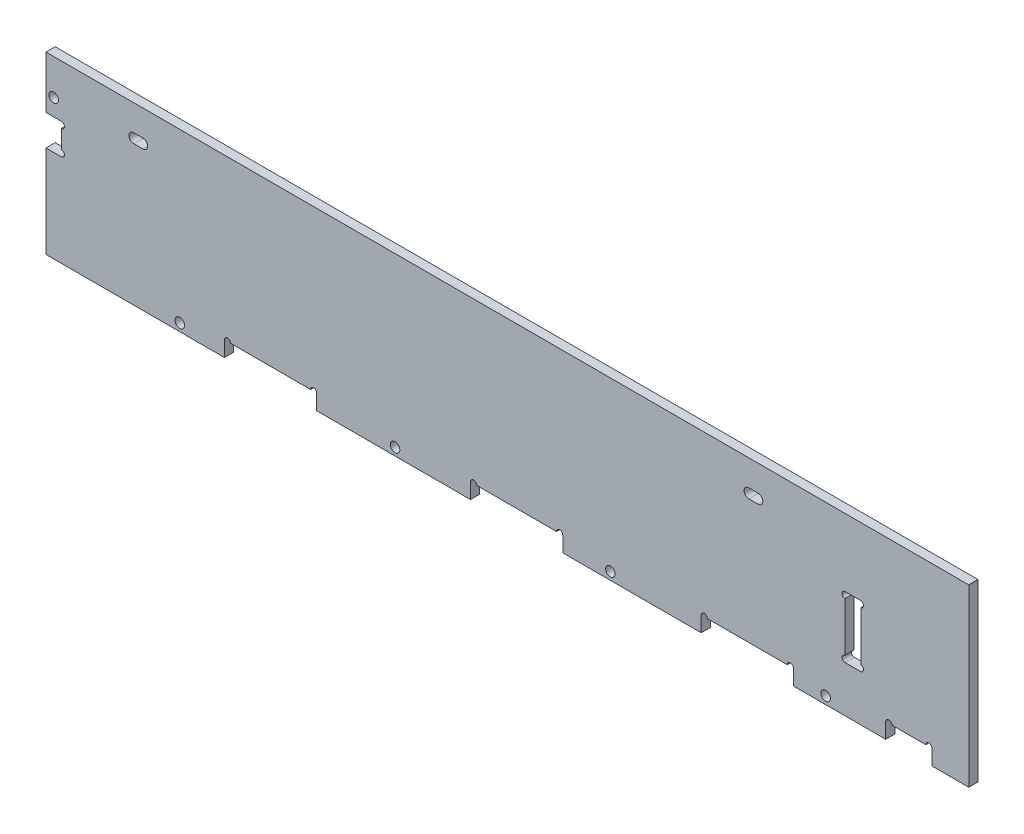
SolidWorks part; units mm, degrees
material "사용자정의 플라스틱"
ref_plane "정면" through (0, 0, 0) normal (0, 0, 1) x (1, 0, 0)
ref_plane "윗면" through (0, 0, 0) normal (0, 1, 0) x (1, 0, 0)
ref_plane "우측면" through (0, 0, 0) normal (1, 0, 0) x (0, 0, -1)
sketch "스케치1" plane through (0, 0, 0) normal (0, 0, 1) x (1, 0, 0)
  line L1 (0, 0) -> (300, 0)
  line L2 (0, 0) -> (0, 57)
  line L3 (0, 57) -> (300, 57)
  line L4 (300, 0) -> (300, 57)
  dimension "D1" = 57
  dimension "D2" = 300
extrude "보스-돌출1" add sketch "스케치1" along normal blind 3
sketch "스케치2" plane through (0, 0, 3) normal (0, 0, 1) x (1, 0, 0)
  line L0 (0, 57) -> (0, 0) construction
  line L1 (5, 40) -> (0, 40)
  line L2 (5, 40) -> (5, 30)
  line L3 (5, 30) -> (0, 30)
  line L4 (0, 40) -> (0, 30)
  line L5 (5, 30) -> (0, 30) construction
  line L6 (0, 0) -> (300, 0) construction
  line L7 (58, 5) -> (88, 5)
  line L8 (58, 5) -> (58, 0)
  line L9 (58, 0) -> (88, 0)
  line L10 (88, 5) -> (88, 0)
  line L11 (88, 5) -> (88, 0) construction
  line L12 (168, 5) -> (168, 0) construction
  line L13 (168, 0) -> (138, 0)
  line L14 (168, 0) -> (168, 5)
  line L15 (168, 5) -> (138, 5)
  line L16 (138, 0) -> (138, 5)
  line L17 (243, 5) -> (243, 0) construction
  line L18 (243, 0) -> (213, 0)
  line L19 (243, 0) -> (243, 5)
  line L20 (243, 5) -> (213, 5)
  line L21 (213, 0) -> (213, 5)
  line L22 (288, 5) -> (288, 0) construction
  line L23 (288, 0) -> (273, 0)
  line L24 (288, 0) -> (288, 5)
  line L25 (288, 5) -> (273, 5)
  line L26 (273, 0) -> (273, 5)
  line L28 (259.8, 35) -> (264.8, 35)
  line L29 (259.8, 35) -> (259.8, 15)
  line L30 (259.8, 15) -> (264.8, 15)
  line L31 (264.8, 35) -> (264.8, 15)
extrude "컷-돌출1" cut sketch "스케치2" against normal blind 5
sketch "스케치3" plane through (0, 0, 3) normal (0, 0, 1) x (1, 0, 0)
  line L0 (264.8, 35) -> (259.8, 35) construction
  line L1 (259.8, 15) -> (264.8, 15) construction
  line L2 (264.8, 15) -> (264.8, 35) construction
  line L3 (259.8, 35) -> (259.8, 15) construction
  line L4 (243, 5) -> (213, 5) construction
  line L5 (88, 5) -> (58, 5) construction
  line L6 (168, 5) -> (138, 5) construction
  line L7 (5, 30) -> (5, 40) construction
  line L8 (288, 5) -> (273, 5) construction
  line L9 (273, 5) -> (273, 0) construction
  line L10 (288, 0) -> (288, 5) construction
  circle A0 centre (274, 5) radius 1
  circle A1 centre (287, 5) radius 1
  circle A2 centre (259.8, 16) radius 1
  circle A3 centre (264.8, 16) radius 1
  circle A4 centre (264.8, 34) radius 1
  circle A5 centre (259.8, 34) radius 1
  circle A6 centre (214, 5) radius 1
  circle A7 centre (242, 5) radius 1
  circle A8 centre (87, 5) radius 1
  circle A9 centre (139, 5) radius 1
  circle A10 centre (167, 5) radius 1
  circle A11 centre (5, 31) radius 1
  circle A12 centre (5, 39) radius 1
  circle A13 centre (59, 5) radius 1
  dimension "D1" = 2
  dimension "D2" = 2
extrude "컷-돌출2" cut sketch "스케치3" against normal blind 5
sketch "스케치4" plane through (0, 0, 0) normal (0, 0, -1) x (-1, 0, 0)
  line L0 (-45.0287, 2.5) -> (-41.9287, 2.5) construction
  line L1 (-2.5, 43.9) -> (-2.5, 47) construction
  line L2 (-5, 43.9) -> (0, 43.9) construction
  line L3 (-45.0287, 5) -> (-45.0287, 0) construction
  line L4 (-5, 47) -> (0, 47) construction
  line L6 (-41.9287, 5) -> (-41.9287, 0) construction
  line L9 (-115.0287, 2.5) -> (-111.9287, 2.5) construction
  line L10 (-115.0287, 5) -> (-115.0287, 0) construction
  line L11 (-111.9287, 5) -> (-111.9287, 0) construction
  line L12 (-185.0287, 2.5) -> (-181.9287, 2.5) construction
  line L13 (-185.0287, 5) -> (-185.0287, 0) construction
  line L14 (-181.9287, 5) -> (-181.9287, 0) construction
  line L15 (-255.0287, 2.5) -> (-251.9287, 2.5) construction
  line L16 (-255.0287, 5) -> (-255.0287, 0) construction
  line L17 (-251.9287, 5) -> (-251.9287, 0) construction
  circle A0 centre (-253.4787, 2.5) radius 1.55
  circle A1 centre (-183.4787, 2.5) radius 1.55
  circle A2 centre (-113.4787, 2.5) radius 1.55
  circle A3 centre (-43.4787, 2.5) radius 1.55
  circle A4 centre (-2.5, 45.45) radius 1.55
extrude "컷-돌출3" cut sketch "스케치4" against normal blind 10
sketch "스케치5" plane through (0, 0, 3) normal (0, 0, 1) x (1, 0, 0)
  line L0 (43.45, 57) -> (43.45, 49)
  line L1 (46.55, 45) -> (43.45, 45) construction
  line L2 (47.75, 49) -> (47.75, 46.2) construction
  line L3 (43.45, 49) -> (43.45, 46.2) construction
  line L4 (46.55, 57) -> (43.45, 57)
  line L5 (47.75, 46.2) -> (46.55, 46.2)
  line L6 (46.55, 57) -> (46.55, 49)
  line L7 (42.25, 46.2) -> (42.25, 49) construction
  line L8 (46.55, 49) -> (47.75, 49)
  line L9 (46.55, 46.2) -> (46.55, 49) construction
  line L10 (43.45, 46.2) -> (43.45, 45)
  line L11 (46.55, 49) -> (43.45, 49) construction
  line L12 (46.55, 46.2) -> (43.45, 46.2) construction
  line L13 (43.45, 46.2) -> (42.25, 46.2)
  line L14 (46.55, 46.2) -> (46.55, 45)
  line L15 (45, 45) -> (45, 43.45) construction
  line L16 (42.25, 49) -> (43.45, 49)
  line L17 (47.75, 47.6) -> (46.55, 47.6) construction
  line L18 (42.25, 47.6) -> (43.45, 47.6) construction
  line L19 (45, 46.2) -> (45, 45) construction
  line L20 (42.25, 47.6) -> (40.85, 47.6) construction
  line L21 (47.75, 47.6) -> (49.15, 47.6) construction
  line L22 (0, 57) -> (45, 57) construction
  line L23 (300, 57) -> (0, 57) construction
  line L24 (45, 57) -> (150, 57) construction
  line L25 (150, 57) -> (255, 57) construction
  line L26 (255, 57) -> (300, 57) construction
  line L49 (151.55, 49) -> (152.75, 49)
  line L50 (151.55, 49) -> (148.45, 49) construction
  line L51 (148.45, 46.2) -> (148.45, 45)
  line L52 (147.25, 46.2) -> (147.25, 49) construction
  line L53 (148.45, 57) -> (148.45, 49)
  line L54 (151.55, 57) -> (151.55, 49)
  line L55 (151.55, 46.2) -> (151.55, 45)
  line L56 (150, 46.2) -> (150, 45) construction
  line L57 (151.55, 46.2) -> (151.55, 49) construction
  line L58 (152.75, 47.6) -> (154.15, 47.6) construction
  line L59 (152.75, 46.2) -> (151.55, 46.2)
  line L60 (148.45, 49) -> (148.45, 46.2) construction
  line L61 (147.25, 47.6) -> (145.85, 47.6) construction
  line L62 (151.55, 57) -> (148.45, 57)
  line L63 (148.45, 46.2) -> (147.25, 46.2)
  line L64 (151.55, 46.2) -> (148.45, 46.2) construction
  line L65 (151.55, 45) -> (148.45, 45) construction
  line L66 (147.25, 47.6) -> (148.45, 47.6) construction
  line L67 (147.25, 49) -> (148.45, 49)
  line L68 (152.75, 49) -> (152.75, 46.2) construction
  line L69 (150, 45) -> (150, 43.45) construction
  line L70 (152.75, 47.6) -> (151.55, 47.6) construction
  line L71 (256.55, 49) -> (257.75, 49)
  line L72 (256.55, 49) -> (253.45, 49) construction
  line L73 (253.45, 46.2) -> (253.45, 45)
  line L74 (252.25, 46.2) -> (252.25, 49) construction
  line L75 (253.45, 57) -> (253.45, 49)
  line L76 (256.55, 57) -> (256.55, 49)
  line L77 (256.55, 46.2) -> (256.55, 45)
  line L78 (255, 46.2) -> (255, 45) construction
  line L79 (256.55, 46.2) -> (256.55, 49) construction
  line L80 (257.75, 47.6) -> (259.15, 47.6) construction
  line L81 (257.75, 46.2) -> (256.55, 46.2)
  line L82 (253.45, 49) -> (253.45, 46.2) construction
  line L83 (252.25, 47.6) -> (250.85, 47.6) construction
  line L84 (256.55, 57) -> (253.45, 57)
  line L85 (253.45, 46.2) -> (252.25, 46.2)
  line L86 (256.55, 46.2) -> (253.45, 46.2) construction
  line L87 (256.55, 45) -> (253.45, 45) construction
  line L88 (252.25, 47.6) -> (253.45, 47.6) construction
  line L89 (252.25, 49) -> (253.45, 49)
  line L90 (257.75, 49) -> (257.75, 46.2) construction
  line L91 (255, 45) -> (255, 43.45) construction
  line L92 (257.75, 47.6) -> (256.55, 47.6) construction
  arc A0 (43.45, 45) -> (46.55, 45) centre (45, 45) ccw
  arc A1 (47.75, 46.2) -> (47.75, 49) centre (47.75, 47.6) ccw
  arc A2 (42.25, 49) -> (42.25, 46.2) centre (42.25, 47.6) ccw
  arc A6 (152.75, 46.2) -> (152.75, 49) centre (152.75, 47.6) ccw
  arc A7 (147.25, 49) -> (147.25, 46.2) centre (147.25, 47.6) ccw
  arc A8 (148.45, 45) -> (151.55, 45) centre (150, 45) ccw
  arc A9 (257.75, 46.2) -> (257.75, 49) centre (257.75, 47.6) ccw
  arc A10 (252.25, 49) -> (252.25, 46.2) centre (252.25, 47.6) ccw
  arc A11 (253.45, 45) -> (256.55, 45) centre (255, 45) ccw
  dimension "D1" = 3.1
  dimension "D2" = 5.5
  dimension "D3" = 2.8
  dimension "D4" = 1.2
  dimension "D5" = 8
  dimension "D6" = 3.1
  dimension "D7" = 45
  dimension "D14" = 3.1
  dimension "D15" = 5.5
  dimension "D16" = 2.8
  dimension "D17" = 1.2
  dimension "D18" = 8
  dimension "D19" = 3.1
  dimension "D20" = 3.1
  dimension "D21" = 5.5
  dimension "D22" = 2.8
  dimension "D23" = 1.2
  dimension "D24" = 8
  dimension "D25" = 3.1
extrude "컷-돌출4" [suppressed] cut sketch "스케치5" against normal blind 10
sketch "스케치7" plane through (0, 0, 3) normal (0, 0, 1) x (1, 0, 0)
  line L0 (259.8, 33) -> (259.8, 17) construction
  line L1 (259.7, 33.9113) -> (264.9, 33.9113)
  line L2 (259.7, 33.9113) -> (259.7, 16.1106)
  line L3 (259.7, 16.1106) -> (264.9, 16.1106)
  line L4 (264.9, 33.9113) -> (264.9, 16.1106)
  line L5 (264.8, 17) -> (264.8, 33) construction
  dimension "D1" = 0.1
  dimension "D2" = 0.1
extrude "컷-돌출5" cut sketch "스케치7" against normal blind 10
sketch "스케치8" plane through (0, 0, 3) normal (0, 0, 1) x (1, 0, 0)
  line L0 (28.5, 47) -> (31.5, 47) construction
  line L1 (28.5, 48.55) -> (31.5, 48.55)
  line L2 (28.5, 45.45) -> (31.5, 45.45)
  line L3 (228.5, 47) -> (231.5, 47) construction
  line L4 (228.5, 48.55) -> (231.5, 48.55)
  line L5 (228.5, 45.45) -> (231.5, 45.45)
  line L6 (230, 47) -> (30, 47) construction
  line L7 (30, 47) -> (0, 47) construction
  line L8 (0, 57) -> (0, 40) construction
  line L9 (300, 57) -> (0, 57) construction
  arc A0 (28.5, 48.55) -> (28.5, 45.45) centre (28.5, 47) ccw
  arc A1 (31.5, 45.45) -> (31.5, 48.55) centre (31.5, 47) ccw
  arc A2 (228.5, 48.55) -> (228.5, 45.45) centre (228.5, 47) ccw
  arc A3 (231.5, 45.45) -> (231.5, 48.55) centre (231.5, 47) ccw
  point P2 (30, 47)
  point P7 (230, 47)
  dimension "D2" = 1.55
  dimension "D1" = 10
  dimension "D3" = 3
  dimension "D4" = 200
  dimension "D5" = 30
extrude "컷-돌출6" cut sketch "스케치8" against normal blind 10
